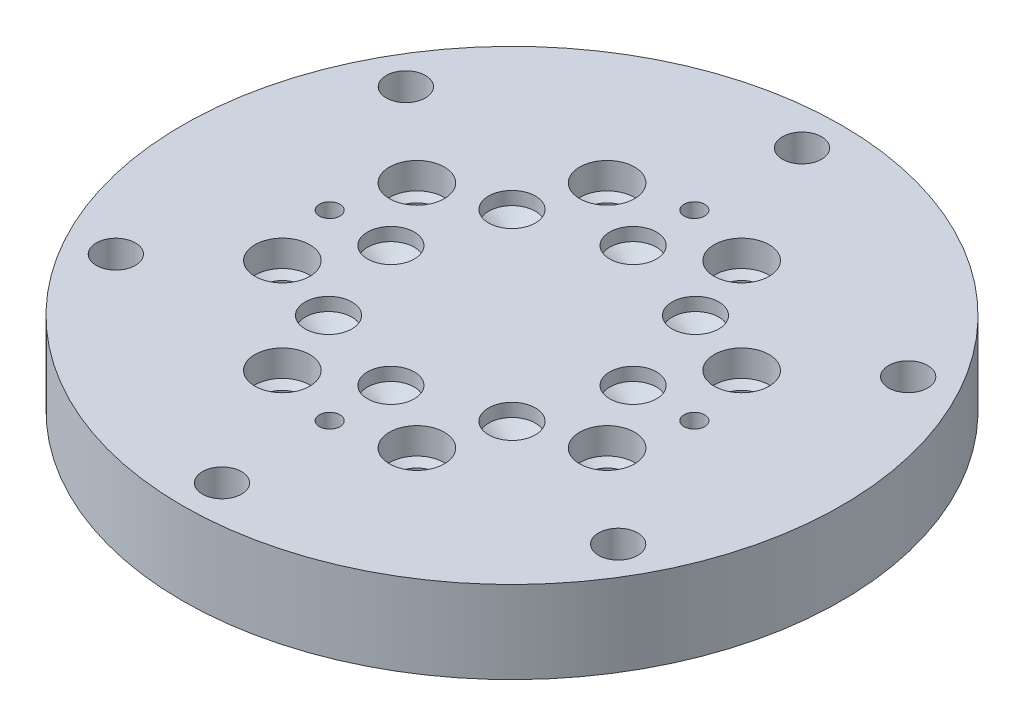
SolidWorks part; units mm, degrees
material "Copper"
ref_plane "Front Plane" through (0, 0, 0) normal (0, 0, 1) x (1, 0, 0)
ref_plane "Top Plane" through (0, 0, 0) normal (0, 1, 0) x (1, 0, 0)
ref_plane "Right Plane" through (0, 0, 0) normal (1, 0, 0) x (0, 0, -1)
ref_axis "Y Axis" through (0, 0.1588, 0) along (0, -1, 0)
sketch "outer" plane through (0, 0, 0) normal (0, 1, 0) x (1, 0, 0)
  circle A0 centre (0, 0) radius 19.05
  dimension "D1" = 38.1
extrude "Body" add sketch "outer" against normal blind 4.7625
sketch "Screw Position" plane through (0, 0, 0) normal (0, 1, 0) x (1, 0, 0)
  point P0 (0, -16.764)
  dimension "D1" = 16.764
hole_wizard "#4-40 Tapped Hole" positions "Sketch12" profile "Sketch13" tap size "#4-40" standard "ANSI Inch" end condition through all
sketch "Sketch12" plane through (0, 0, 0) normal (0, 1, 0) x (1, 0, 0)
  point P0 (0, -16.764)
sketch "Sketch13" plane through (0, 0, 16.764) normal (1, 0, 0) x (0, 0, 1)
  line L0 (0, 0) -> (0, 4.7625)
  line L1 (0, 4.7625) -> (1.1303, 4.7625)
  line L2 (1.1303, 4.7625) -> (1.1303, 0)
  line L5 (1.1303, 0) -> (0, 0)
  line L11 (0, -6.35) -> (0, 107.95) construction
  dimension "Thru Tap Drill Dia." = 2.2606
  dimension "Thru Tap Drill Depth" = 4.7625
cosmetic thread "Hole Thread3" parameters "D2"=2.8448
pattern_circular "Screw Holes" count 6 over 360 about axis through (0, 0.1588, 0) along (0, -1, 0) of "#4-40 Tapped Hole"
sketch "inner" plane through (0, 0, 0) normal (0, 1, 0) x (1, 0, 0)
  circle A0 centre (0, 0) radius 11.938
  dimension "D1" = 23.876
sketch "Inner Screw Position" plane through (0, 0, 0) normal (0, 1, 0) x (1, 0, 0)
  point P0 (0, 10.541)
  dimension "D1" = 10.541
hole_wizard "#0-80 Tapped Hole" positions "Sketch34" profile "Sketch35" tap size "#0-80" standard "ANSI Inch" end condition through all
sketch "Sketch34" plane through (0, 0, 0) normal (0, 1, 0) x (1, 0, 0)
  point P0 (0, 10.541)
sketch "Sketch35" plane through (0, 0, -10.541) normal (1, 0, 0) x (0, 0, 1)
  line L0 (0, 0) -> (0, 4.7625)
  line L1 (0, 4.7625) -> (0.5956, 4.7625)
  line L2 (0.5956, 4.7625) -> (0.5956, 0)
  line L5 (0.5956, 0) -> (0, 0)
  line L11 (0, -6.35) -> (0, 107.95) construction
  dimension "Thru Tap Drill Dia." = 1.1913
  dimension "Thru Tap Drill Depth" = 4.7625
cosmetic thread "Hole Thread4" parameters "D2"=1.524
pattern_circular "Inner Screw Holes" count 4 over 360 about axis through (0, 0.1588, 0) along (0, -1, 0) of "#0-80 Tapped Hole"
sketch "IO Hole Location" plane through (0, 0, 0) normal (0, 1, 0) x (1, 0, 0)
  point P0 (-3.8881, 9.3866)
hole_wizard "#43 (0.089) Diameter Hole1" positions "Sketch36" profile "Sketch37" hole size "#43" standard "ANSI Inch" end condition through all
sketch "Sketch36" plane through (0, 0, 0) normal (0, 1, 0) x (1, 0, 0)
  point P0 (-3.8881, 9.3866)
sketch "Sketch37" plane through (-3.8881, 0, -9.3866) normal (1, 0, 0) x (0, 0, 1)
  line L0 (0, 0) -> (0, 4.7625)
  line L1 (0, 4.7625) -> (1.1303, 4.7625)
  line L2 (1.1303, 4.7625) -> (1.1303, 0)
  line L5 (1.1303, 0) -> (0, 0)
  line L11 (0, -6.35) -> (0, 107.95) construction
  dimension "Thru Hole Dia." = 2.2606
  dimension "Thru Hole Depth" = 4.7625
hole_wizard "1/8 (0.125) Diameter Hole1" positions "Sketch38" profile "Sketch40" hole size "1/8" standard "ANSI Inch"
sketch "Sketch38" plane through (0, 0, 0) normal (0, 1, 0) x (1, 0, 0)
  point P0 (-3.8881, 9.3866)
sketch "Sketch40" plane through (-3.8881, 0, -9.3866) normal (1, 0, 0) x (0, 0, 1)
  line L0 (0, 0) -> (0, 2.4779)
  line L1 (0, 2.4779) -> (1.5875, 1.524)
  line L2 (1.5875, 1.524) -> (1.5875, 0)
  line L5 (1.5875, 0) -> (0, 0)
  line L10 (0, 2.4779) -> (-1.5875, 1.524) construction
  line L11 (0, -6.35) -> (0, 107.95) construction
  dimension "Hole Dia." = 3.175
  dimension "Hole Depth" = 1.524
  dimension "Drill Angle" = 118
hole_wizard "1/8 (0.125) Diameter Hole2" positions "Sketch41" profile "Sketch42" hole size "1/8" standard "ANSI Inch"
sketch "Sketch41" plane through (0, -4.7625, 0) normal (0, -1, 0) x (-1, 0, 0)
  point P0 (3.8881, 9.3866)
sketch "Sketch42" plane through (-3.8881, -4.7625, -9.3866) normal (1, 0, 0) x (0, 0, -1)
  line L0 (0, 0) -> (0, 2.4779)
  line L1 (0, 2.4779) -> (1.5875, 1.524)
  line L2 (1.5875, 1.524) -> (1.5875, 0)
  line L5 (1.5875, 0) -> (0, 0)
  line L10 (0, 2.4779) -> (-1.5875, 1.524) construction
  line L11 (0, -6.35) -> (0, 107.95) construction
  dimension "Hole Dia." = 3.175
  dimension "Hole Depth" = 1.524
  dimension "Drill Angle" = 118
pattern_circular "IO Holes Pattern" count 8 over 360 about axis through (0, 0.1588, 0) along (0, -1, 0) of "#43 (0.089) Diameter Hole1", "1/8 (0.125) Diameter Hole1", "1/8 (0.125) Diameter Hole2"
sketch "Post Bottom Location" plane through (0, 0, 0) normal (0, 1, 0) x (1, 0, 0)
  point P0 (0, 7)
  point P1 (-5.3033, 5.3033)
  dimension "D1" = 7
  dimension "D2" = 7.5
hole_wizard "#36 (0.1065) Diameter Hole1" positions "Sketch44" profile "Sketch45" hole size "#36" standard "ANSI Inch"
sketch "Sketch44" plane through (0, 0, 0) normal (0, 1, 0) x (1, 0, 0)
  point P0 (0, 7)
  point P3 (-5.3033, 5.3033)
sketch "Sketch45" plane through (0, 0, -7) normal (1, 0, 0) x (0, 0, 1)
  line L0 (0, 0) -> (0, 1.5747)
  line L1 (0, 1.5747) -> (1.3525, 0.762)
  line L2 (1.3525, 0.762) -> (1.3525, 0)
  line L5 (1.3525, 0) -> (0, 0)
  line L10 (0, 1.5747) -> (-1.3525, 0.762) construction
  line L11 (0, -6.35) -> (0, 107.95) construction
  dimension "Hole Dia." = 2.7051
  dimension "Hole Depth" = 0.762
  dimension "Drill Angle" = 118
pattern_circular "Post Bottoms" count 4 over 360 about axis through (0, 0.1588, 0) along (0, -1, 0) of "#36 (0.1065) Diameter Hole1"
equation "\"outer_d\"= 3 / 2in"
equation "\"screw_r\" = 0.66in"
equation "\"inner_d\" = 0.940in"
equation "\"bottom_h\"= 3 / 16in"
equation "\"pocket_h\"= 0.060in"
equation "\"screw_inner_r\"= 0.415in"
equation "\"io_r\"= 0.4in"
equation "\"D1@outer\" = \"outer_d\""
equation "\"D1@Body\" = \"bottom_h\""
equation "\"D1@inner\" = \"inner_d\""
equation "\"D1@Screw Position\" = \"screw_r\""
equation "\"D1@Inner Screw Position\" = \"screw_inner_r\""
equation "\"D1@IO Hole Location\"=\"io_r\""
equation "\"post_r1\" = 7mm"
equation "\"post_r2\" = 7.5mm"
equation "\"D1@Post Bottom Location\" = \"post_r1\""
equation "\"D2@Post Bottom Location\" = \"post_r2\""
equation "\"post_bottom_h\"= 0.03in"
